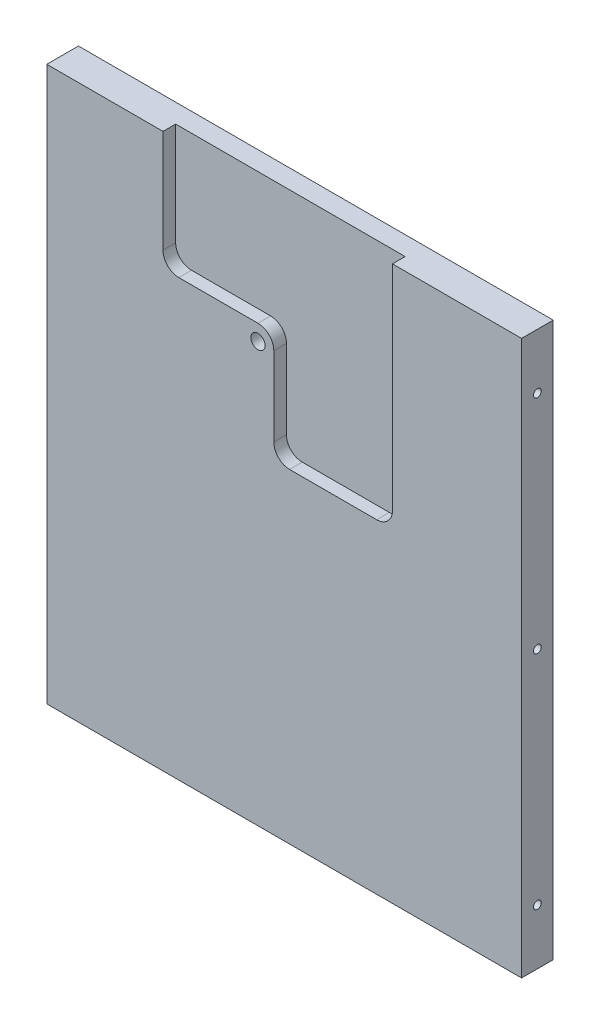
SolidWorks part; units mm, degrees
material "AISI 1020"
ref_plane "Ebene vorne" through (0, 0, 0) normal (0, 0, 1) x (1, 0, 0)
ref_plane "Ebene oben" through (0, 0, 0) normal (0, 1, 0) x (1, 0, 0)
ref_plane "Ebene rechts" through (0, 0, 0) normal (1, 0, 0) x (0, 0, -1)
sketch "Skizze1" plane through (0, 0, 0) normal (0, 0, 1) x (1, 0, 0)
  line L1 (-96.1409, 69.4002) -> (53.8591, 69.4002)
  line L2 (-96.1409, 69.4002) -> (-96.1409, -105.5998)
  line L3 (-96.1409, -105.5998) -> (53.8591, -105.5998)
  line L4 (53.8591, 69.4002) -> (53.8591, -105.5998)
  dimension "D1" = 150
  dimension "D2" = 175
extrude "Aufsatz-Linear austragen1" add sketch "Skizze1" along normal blind 10
sketch "Skizze2" plane through (0, 0, 10) normal (0, 0, 1) x (1, 0, 0)
  line L0 (-96.1409, -18.0998) -> (53.8591, -18.0998) construction
  line L1 (-96.1409, 69.4002) -> (-96.1409, -105.5998) construction
  line L2 (-96.1409, -18.0998) -> (33.5831, 69.4002) construction
  line L3 (53.8591, 69.4002) -> (-96.1409, 69.4002) construction
  line L4 (-96.1409, -18.0998) -> (33.5831, -105.5998) construction
  line L5 (-96.1409, -105.5998) -> (53.8591, -105.5998) construction
  line L6 (-29.4257, 26.9002) -> (53.8591, 26.9002) construction
  line L11 (53.8591, -105.5998) -> (53.8591, 69.4002) construction
  line L12 (-29.4257, -63.0998) -> (-29.4257, 26.9002) construction
  line L13 (53.8591, -8.0998) -> (-96.1409, -8.0998) construction
  line L14 (53.8591, -28.0998) -> (-96.1409, -28.0998) construction
  line L15 (-21.1409, -28.0998) -> (-21.1409, -8.0998) construction
  circle A0 centre (-29.4257, 26.9002) radius 2.25
  point P29 (-21.1409, -18.0998)
  dimension "D4" = 4.5
  dimension "D1" = 34
  dimension "D2" = 34
  dimension "D3" = 90
  dimension "D10" = 20
extrude "Schnitt-Linear austragen1" cut sketch "Skizze2" against normal blind 10
sketch "Skizze3" plane through (0, 0, 10) normal (0, 0, 1) x (1, 0, 0)
  line L1 (-54.4257, 31.9002) -> (-54.4257, 69.4002) construction
  line L7 (-54.4257, 31.9002) -> (-29.4257, 31.9002)
  line L8 (-24.4257, 26.9002) -> (-24.4257, 1.9002)
  line L9 (-19.4257, -3.0998) -> (8.0743, -3.0998)
  line L10 (13.0743, 1.9002) -> (13.0743, 69.4002)
  line L11 (53.8591, 69.4002) -> (-96.1409, 69.4002) construction
  line L12 (-59.4257, 36.9002) -> (-59.4257, 69.4002)
  line L13 (-59.4257, 69.4002) -> (13.0743, 69.4002)
  line L14 (-24.4257, 1.9002) -> (13.0743, 1.9002) construction
  arc A3 (-29.4257, 31.9002) -> (-24.4257, 26.9002) centre (-29.4257, 26.9002) cw
  arc A4 (-24.4257, 1.9002) -> (-19.4257, -3.0998) centre (-19.4257, 1.9002) ccw
  arc A5 (8.0743, -3.0998) -> (13.0743, 1.9002) centre (8.0743, 1.9002) ccw
  arc A6 (-54.4257, 31.9002) -> (-59.4257, 36.9002) centre (-54.4257, 36.9002) cw
  circle A7 centre (-29.4257, 26.9002) radius 2.25 construction
  dimension "D1" = 5
  dimension "D2" = 25
  dimension "D3" = 25
extrude "Schnitt-Linear austragen2" cut sketch "Skizze3" against normal blind 4
sketch "Skizze4" plane through (-96.1409, 0, 0) normal (-1, 0, 0) x (0, 0, 1)
  line L0 (0, -18.0998) -> (10, -18.0998) construction
  line L1 (5, -88.0998) -> (5, -18.0998) construction
  line L2 (5, -18.0998) -> (5, 51.9002) construction
  line L4 (10, 69.4002) -> (10, -105.5998) construction
  line L5 (0, 69.4002) -> (0, -105.5998) construction
  circle A0 centre (5, 51.9002) radius 1.23
  circle A1 centre (5, -18.0998) radius 1.23
  circle A3 centre (5, -88.0998) radius 1.23
  point P7 (5, -18.0998)
  dimension "D2" = 2.46
  dimension "D1" = 70
extrude "Schnitt-Linear austragen3" cut sketch "Skizze4" against normal blind 5
sketch "Skizze6" plane through (53.8591, 0, 0) normal (1, 0, 0) x (0, 0, -1)
  line L0 (-10, -18.0998) -> (0, -18.0998) construction
  line L1 (-5, -88.0998) -> (-5, -18.0998) construction
  line L2 (-5, -18.0998) -> (-5, 51.9002) construction
  line L4 (0, -105.5998) -> (0, 69.4002) construction
  line L5 (-10, -105.5998) -> (-10, 69.4002) construction
  circle A0 centre (-5, 51.9002) radius 1.23
  circle A1 centre (-5, -18.0998) radius 1.23
  circle A3 centre (-5, -88.0998) radius 1.23
  point P7 (-5, -18.0998)
  dimension "D2" = 2.46
  dimension "D1" = 70
extrude "Schnitt-Linear austragen4" cut sketch "Skizze6" against normal blind 5
sketch "Skizze7" plane through (0, -105.5998, 0) normal (0, -1, 0) x (1, 0, 0)
  line L0 (-29.4209, 0) -> (-29.4209, 10) construction
  line L1 (-96.1409, 0) -> (53.8591, 0) construction
  line L2 (-96.1409, 10) -> (53.8591, 10) construction
  line L3 (-96.1409, 10) -> (-96.1409, 0) construction
  circle A0 centre (-29.4209, 5) radius 1
  dimension "D1" = 2
  dimension "D2" = 66.72
